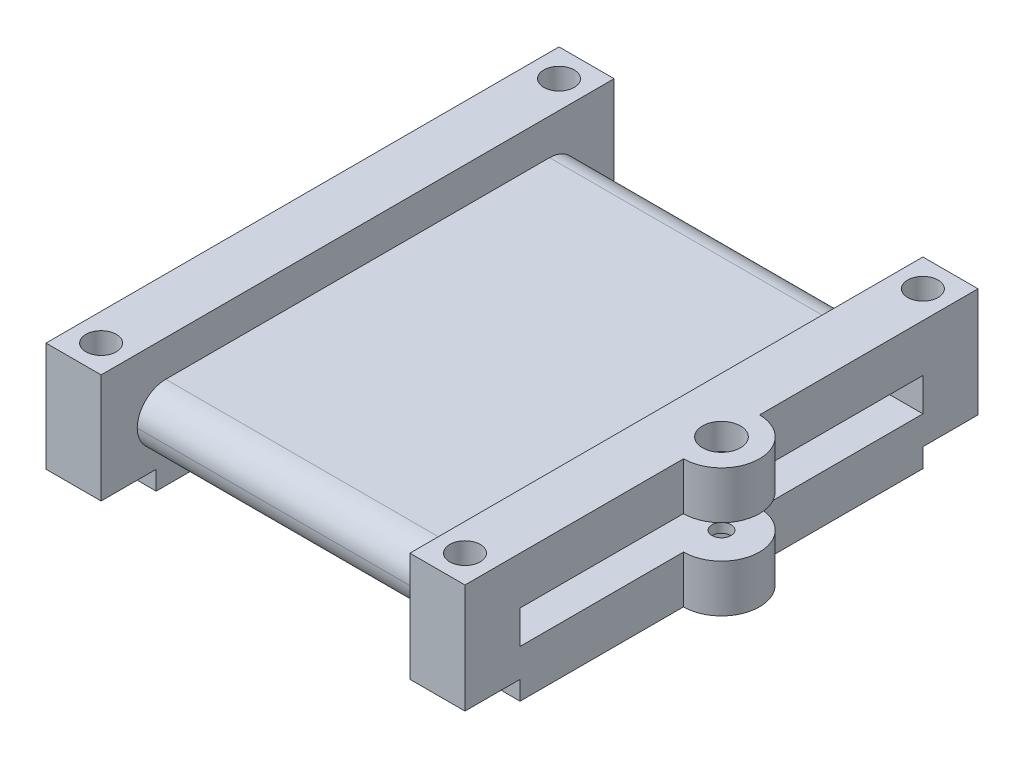
SolidWorks part; units mm, degrees
ref_plane "Front Plane" through (0, 0, 0) normal (0, 0, 1) x (1, 0, 0)
ref_plane "Top Plane" through (0, 0, 0) normal (0, 1, 0) x (1, 0, 0)
ref_plane "Right Plane" through (0, 0, 0) normal (1, 0, 0) x (0, 0, -1)
sketch "Sketch1" plane through (0, 0, 0) normal (1, 0, 0) x (0, 0, -1)
  line L0 (23.2, 5.9) -> (23.2, 0) construction
  line L1 (0, 0) -> (46.4, 0)
  line L2 (0, 0) -> (0, 5.9)
  line L3 (0, 5.9) -> (46.4, 5.9)
  line L4 (46.4, 0) -> (46.4, 5.9)
  line L6 (2, 1.2) -> (44.4, 1.2)
  line L7 (2, 1.2) -> (2, 4.7)
  line L8 (2, 4.7) -> (44.4, 4.7)
  line L9 (44.4, 1.2) -> (44.4, 4.7)
  line L10 (2, 1.2) -> (44.4, 4.7) construction
  line L11 (2, 4.7) -> (44.4, 1.2) construction
  point P7 (23.2, 2.95)
  dimension "D1" = 46.4
  dimension "D2" = 5.9
  dimension "D3" = 3.5
  dimension "D4" = 42.4
extrude "Boss-Extrude1" add sketch "Sketch1" along normal blind 32.5
fillet "Fillet2" radius 3 4 edges at (16.25, 0, -46.4) (16.25, 0, 0) (16.25, 5.9, 0) (16.25, 5.9, -46.4)
sketch "Sketch2" plane through (32.5, 0, 0) normal (1, 0, 0) x (0, 0, -1)
  line L0 (23.2, 5.9) -> (23.2, 0) construction
  line L1 (43.4, 5.9) -> (3, 5.9) construction
  line L2 (3, 0) -> (43.4, 0) construction
  line L4 (-3.8, -3.8) -> (50.2, -3.8)
  line L5 (-3.8, -3.8) -> (-3.8, 9.7)
  line L6 (-3.8, 9.7) -> (50.2, 9.7)
  line L7 (50.2, -3.8) -> (50.2, 9.7)
  line L8 (-3.8, -3.8) -> (50.2, 9.7) construction
  line L9 (-3.8, 9.7) -> (50.2, -3.8) construction
  line L14 (44.4, 1.2) -> (2, 1.2)
  line L15 (44.4, 1.2) -> (44.4, 4.7)
  line L16 (44.4, 4.7) -> (2, 4.7)
  line L17 (2, 1.2) -> (2, 4.7)
  line L18 (44.4, 1.2) -> (2, 4.7) construction
  line L19 (44.4, 4.7) -> (2, 1.2) construction
  point P6 (23.2, 2.95)
  point P11 (23.2, 2.95)
  point P12 (23.2, 2.95)
  dimension "D1" = 13.5
  dimension "D2" = 54
extrude "Boss-Extrude2" add sketch "Sketch2" along normal blind 5.8
sketch "Sketch3" plane through (0, 0, 0) normal (-1, 0, 0) x (0, 0, 1)
  line L0 (-23.2, 5.9) -> (-23.2, 0) construction
  line L1 (-43.4, 5.9) -> (-3, 5.9) construction
  line L2 (-3, 0) -> (-43.4, 0) construction
  line L4 (3.8, -3.8) -> (-50.2, -3.8)
  line L5 (3.8, -3.8) -> (3.8, 9.7)
  line L6 (3.8, 9.7) -> (-50.2, 9.7)
  line L7 (-50.2, -3.8) -> (-50.2, 9.7)
  line L8 (3.8, -3.8) -> (-50.2, 9.7) construction
  line L9 (3.8, 9.7) -> (-50.2, -3.8) construction
  line L10 (-2, 1.2) -> (-44.4, 1.2)
  line L11 (-2, 1.2) -> (-2, 4.7)
  line L12 (-2, 4.7) -> (-44.4, 4.7)
  line L13 (-44.4, 1.2) -> (-44.4, 4.7)
  line L14 (-2, 1.2) -> (-44.4, 4.7) construction
  line L15 (-2, 4.7) -> (-44.4, 1.2) construction
  point P6 (-23.2, 2.95)
  point P12 (-23.2, 2.95)
extrude "Boss-Extrude3" add sketch "Sketch3" along normal blind 5.8
sketch "Sketch4" plane through (0, 9.7, 0) normal (0, 1, 0) x (1, 0, 0)
  line L0 (-2.9, 50.2) -> (-2.9, 47.3) construction
  line L1 (-5.8, 50.2) -> (0, 50.2) construction
  line L2 (35.4, 50.2) -> (35.4, 47.3) construction
  line L3 (38.3, 50.2) -> (32.5, 50.2) construction
  line L4 (-2.9, -3.8) -> (-2.9, -0.9) construction
  line L5 (-5.8, -3.8) -> (0, -3.8) construction
  line L6 (35.4, -3.8) -> (35.4, -0.9) construction
  line L7 (38.3, -3.8) -> (32.5, -3.8) construction
  circle A0 centre (-2.9, 47.3) radius 1.6
  circle A1 centre (35.4, 47.3) radius 1.6
  circle A2 centre (-2.9, -0.9) radius 1.6
  circle A3 centre (35.4, -0.9) radius 1.6
  dimension "D2" = 3.2
  dimension "D4" = 3.2
  dimension "D6" = 3.2
  dimension "D8" = 3.2
  dimension "D1" = 2.9
  dimension "D3" = 2.9
  dimension "D5" = 2.9
  dimension "D7" = 2.9
extrude "Cut-Extrude1" cut sketch "Sketch4" against normal through all
sketch "Sketch6" plane through (38.3, 0, 0) normal (1, 0, 0) x (0, 0, -1)
  line L0 (50.2, -3.8) -> (50.2, 9.7) construction
  line L1 (-3.8, -3.8) -> (50.2, -3.8)
  line L2 (-3.8, -3.8) -> (-3.8, 3.4)
  line L3 (-3.8, 3.4) -> (50.2, 3.4)
  line L4 (50.2, -3.8) -> (50.2, 3.4)
  dimension "D1" = 7.2
extrude "Cut-Extrude2" [suppressed] cut sketch "Sketch6" against normal blind 5.8
sketch "Sketch7" plane through (-5.8, 0, 0) normal (-1, 0, 0) x (0, 0, 1)
  line L0 (3.8, -3.8) -> (3.8, 9.7) construction
  line L1 (-50.2, -3.8) -> (3.8, -3.8)
  line L2 (-50.2, -3.8) -> (-50.2, 3.4)
  line L3 (-50.2, 3.4) -> (3.8, 3.4)
  line L4 (3.8, -3.8) -> (3.8, 3.4)
  dimension "D1" = 7.2
extrude "Cut-Extrude3" [suppressed] cut sketch "Sketch7" against normal blind 5.8
sketch "Sketch8" plane through (0, 9.7, 0) normal (0, 1, 0) x (1, 0, 0)
  line L0 (38.3, 50.2) -> (38.3, -3.8) construction
  circle A0 centre (38.3, 23.2) radius 4
  dimension "D1" = 8
extrude "Boss-Extrude4" add sketch "Sketch8" against normal blind 13.5
hole_wizard "CSK for M2 Flat Head Machine Screw1" positions "Sketch12" profile "Sketch13" countersink size "M2" standard "ANSI Metric" end condition through all
sketch "Sketch12" plane through (0, 9.7, 0) normal (0, 1, 0) x (1, 0, 0)
  point P0 (38.3, 23.2)
sketch "Sketch13" plane through (38.3, 9.7, -23.2) normal (1, 0, 0) x (0, 0, 1)
  line L0 (0, 0) -> (0, 13.5)
  line L1 (0, 13.5) -> (1, 13.5)
  line L2 (1, 13.5) -> (1, 3.75)
  line L3 (1, 3.75) -> (2, 2.75)
  line L4 (2, 2.75) -> (2, 0)
  line L6 (2, 0) -> (0, 0)
  line L7 (-1, 3.75) -> (-2, 2.75) construction
  line L11 (0, -6.35) -> (0, 107.95) construction
  dimension "Thru Hole Dia." = 2
  dimension "Thru Hole Depth" = 13.5
  dimension "C'Sink Dia." = 4
  dimension "C'Sink Angle" = 90
  dimension "Head Clearance" = 2.75
sketch "Sketch14" plane through (0, -3.8, 0) normal (0, -1, 0) x (1, 0, 0)
  line L1 (38.3, -20.7751) -> (36.2, -21.9876)
  line L2 (36.2, -21.9876) -> (36.2, -24.4124)
  line L3 (36.2, -24.4124) -> (38.3, -25.6249)
  line L4 (38.3, -25.6249) -> (40.4, -24.4124)
  line L5 (40.4, -24.4124) -> (40.4, -21.9876)
  line L6 (40.4, -21.9876) -> (38.3, -20.7751)
  circle A0 centre (38.3, -23.2) radius 2.1 construction
  dimension "D1" = 4.2
extrude "Cut-Extrude4" cut sketch "Sketch14" against normal blind 4
sketch "Sketch15" plane through (-5.8, 0, 0) normal (-1, 0, 0) x (0, 0, 1)
  line L1 (-44.4, 1.2) -> (-2, 1.2)
  line L2 (-44.4, 1.2) -> (-44.4, 4.7)
  line L3 (-44.4, 4.7) -> (-2, 4.7)
  line L4 (-2, 1.2) -> (-2, 4.7)
  line L5 (-50.2, -3.8) -> (-44.4, -3.8)
  line L6 (-50.2, -3.8) -> (-50.2, -1.8)
  line L7 (-50.2, -1.8) -> (-44.4, -1.8)
  line L8 (-44.4, -3.8) -> (-44.4, -1.8)
  line L9 (3.8, -3.8) -> (-2, -3.8)
  line L10 (3.8, -3.8) -> (3.8, -1.8)
  line L11 (3.8, -1.8) -> (-2, -1.8)
  line L12 (-2, -3.8) -> (-2, -1.8)
  dimension "D1" = 5.8
  dimension "D2" = 2
  dimension "D3" = 5.8
  dimension "D4" = 2
extrude "Cut-Extrude5" cut sketch "Sketch15" against normal through all
fillet "Fillet3" radius 2 1 edges at (-5.8, -3.8, -23.2)
